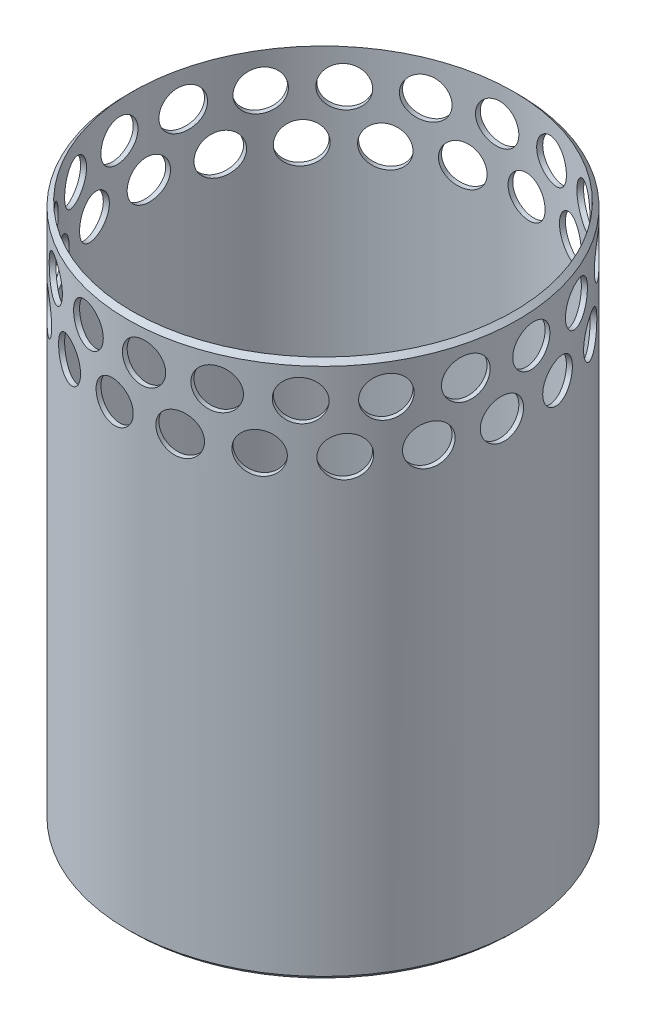
SolidWorks part; units mm, degrees
material "Plain Carbon Steel"
ref_plane "Front Plane" through (0, 0, 0) normal (0, 0, 1) x (1, 0, 0)
ref_plane "Top Plane" through (0, 0, 0) normal (0, 1, 0) x (1, 0, 0)
ref_plane "Right Plane" through (0, 0, 0) normal (1, 0, 0) x (0, 0, -1)
sketch "Sketch1" plane through (0, 0, 0) normal (0, 1, 0) x (1, 0, 0)
  circle A0 centre (0, 0) radius 80.55
  circle A1 centre (0, 0) radius 82.55
  dimension "D1" = 165.1
  dimension "D2" = 2
extrude "Boss-Extrude1" add sketch "Sketch1" along normal blind 227.4
chamfer "Chamfer1" distance 2 angle 45 2 edges at (0, 0, 82.55) (0, 227.4, 82.55)
sketch "Sketch2" plane through (0, 0, 0) normal (0, 0, 1) x (1, 0, 0)
  line L0 (-6.2145, 212.6655) -> (0, 202.4) construction
  line L2 (0, 202.4) -> (6.2145, 192.1345) construction
  line L4 (0, 0) -> (0, 50.3884) construction
  line L5 (80.55, 227.4) -> (-80.55, 227.4) construction
  circle A0 centre (-6.2145, 212.6655) radius 8.5
  circle A1 centre (6.2145, 192.1345) radius 8.5
  dimension "D1" = 17
  dimension "D2" = 12
  dimension "D3" = 25
  dimension "D4" = 31.19
extrude "Cut-Extrude1" cut sketch "Sketch2" against normal through all
ref_axis "Axis1" through (0, 227.4, 0) along (0, -1, 0)
pattern_circular "CirPattern1" count 20 over 360 about axis through (0, 227.4, 0) along (0, -1, 0) of "Cut-Extrude1"
equation "\"TubeDiameter\" = 6.500in"
equation "\"D1@Sketch1\"=\"TubeDiameter\""
